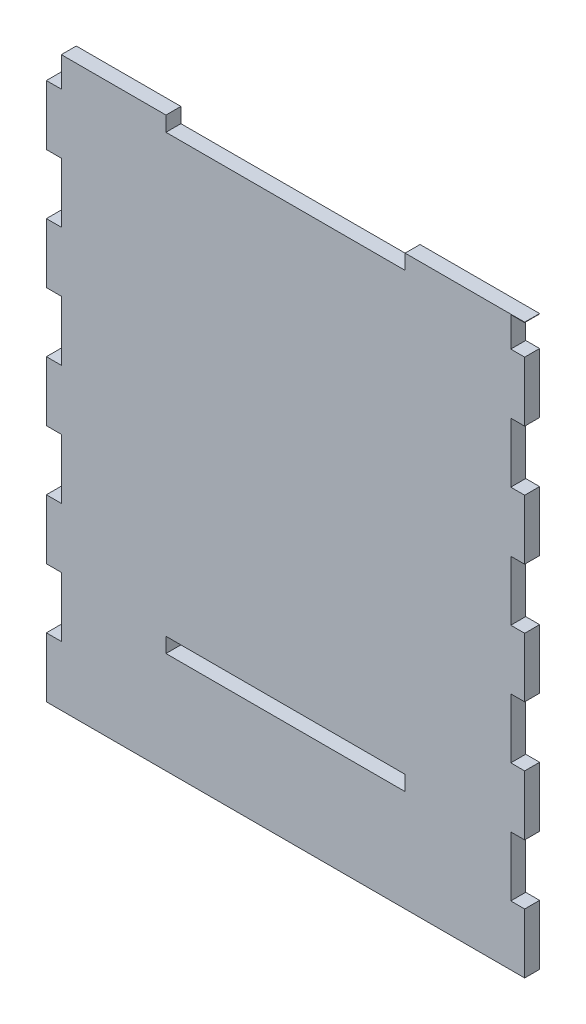
SolidWorks part; units mm, degrees
ref_plane "Front Plane" through (0, 0, 0) normal (0, 0, 1) x (1, 0, 0)
ref_plane "Top Plane" through (0, 0, 0) normal (0, 1, 0) x (1, 0, 0)
ref_plane "Right Plane" through (0, 0, 0) normal (1, 0, 0) x (0, 0, -1)
sketch "Sketch1" plane through (0, 0, 0) normal (0, 0, 1) x (1, 0, 0)
  line L1 (-202.6682, 117.9755) -> (0.5318, 117.9755)
  line L2 (-202.6682, 117.9755) -> (-202.6682, -123.3245)
  line L3 (-202.6682, -123.3245) -> (0.5318, -123.3245)
  line L4 (0.5318, 117.9755) -> (0.5318, -123.3245)
  dimension "D1" = 241.3
  dimension "D2" = 203.2
extrude "Boss-Extrude1" add sketch "Sketch1" along normal blind 6.35
sketch "Sketch2" plane through (0, 0, 6.35) normal (0, 0, 1) x (1, 0, 0)
  line L0 (-202.6682, 117.9755) -> (-202.6682, -123.3245) construction
  line L1 (-202.6682, -97.9245) -> (-196.3182, -97.9245)
  line L2 (-202.6682, -97.9245) -> (-202.6682, -72.5245)
  line L3 (-202.6682, -72.5245) -> (-196.3182, -72.5245)
  line L4 (-196.3182, -97.9245) -> (-196.3182, -72.5245)
  line L5 (-202.6682, -123.3245) -> (0.5318, -123.3245) construction
  line L6 (-202.6682, 117.9755) -> (-202.6682, -123.3245) construction
  line L7 (-202.6682, -47.1245) -> (-196.3182, -47.1245)
  line L8 (-202.6682, -47.1245) -> (-202.6682, -21.7245)
  line L9 (-202.6682, -21.7245) -> (-196.3182, -21.7245)
  line L10 (-196.3182, -47.1245) -> (-196.3182, -21.7245)
  line L11 (-202.6682, 3.6755) -> (-196.3182, 3.6755)
  line L12 (-202.6682, 3.6755) -> (-202.6682, 29.0755)
  line L13 (-202.6682, 29.0755) -> (-196.3182, 29.0755)
  line L14 (-196.3182, 3.6755) -> (-196.3182, 29.0755)
  line L15 (-202.6682, 54.4755) -> (-196.3182, 54.4755)
  line L16 (-202.6682, 54.4755) -> (-202.6682, 79.8755)
  line L17 (-202.6682, 79.8755) -> (-196.3182, 79.8755)
  line L18 (-196.3182, 54.4755) -> (-196.3182, 79.8755)
  line L19 (-202.6682, 105.2755) -> (-196.3182, 105.2755)
  line L20 (-202.6682, 105.2755) -> (-202.6682, 117.9755)
  line L21 (-202.6682, 117.9755) -> (-196.3182, 117.9755)
  line L22 (-196.3182, 105.2755) -> (-196.3182, 117.9755)
  line L23 (0.5318, 117.9755) -> (-202.6682, 117.9755) construction
  line L24 (-5.3773, -97.9245) -> (0.9727, -97.9245)
  line L25 (-5.3773, -97.9245) -> (-5.3773, -72.5245)
  line L26 (-5.3773, -72.5245) -> (0.9727, -72.5245)
  line L27 (0.9727, -97.9245) -> (0.9727, -72.5245)
  line L28 (-5.3773, -47.1245) -> (0.9727, -47.1245)
  line L29 (-5.3773, -47.1245) -> (-5.3773, -21.7245)
  line L30 (-5.3773, -21.7245) -> (0.9727, -21.7245)
  line L31 (0.9727, -47.1245) -> (0.9727, -21.7245)
  line L32 (-5.3773, 3.5082) -> (0.9727, 3.5082)
  line L33 (-5.3773, 3.5082) -> (-5.3773, 28.9082)
  line L34 (-5.3773, 28.9082) -> (0.9727, 28.9082)
  line L35 (0.9727, 3.5082) -> (0.9727, 28.9082)
  line L36 (-5.3773, 54.3082) -> (0.9727, 54.3082)
  line L37 (-5.3773, 54.3082) -> (-5.3773, 79.7082)
  line L38 (-5.3773, 79.7082) -> (0.9727, 79.7082)
  line L39 (0.9727, 54.3082) -> (0.9727, 79.7082)
  line L40 (-5.3773, 105.1082) -> (0.9727, 105.1082)
  line L41 (-5.3773, 105.1082) -> (-5.3773, 117.8082)
  line L42 (-5.3773, 117.8082) -> (0.9727, 117.8082)
  line L43 (0.9727, 105.1082) -> (0.9727, 117.8082)
  dimension "D1" = 6.35
  dimension "D2" = 25.4
  dimension "D3" = 25.4
  dimension "D4" = 25.4
  dimension "D5" = 25.4
  dimension "D6" = 6.35
  dimension "D7" = 12.7
  dimension "D8" = 25.4
  dimension "D9" = 25.4
  dimension "D10" = 25.4
  dimension "D11" = 25.4
  dimension "D12" = 25.4
  dimension "D13" = 25.4
  dimension "D14" = 25.4
  dimension "D15" = 25.4
  dimension "D16" = 6.35
  dimension "D17" = 12.7
  dimension "D18" = 25.4
  dimension "D19" = 25.4
  dimension "D20" = 25.4
  dimension "D21" = 25.4
  dimension "D22" = 25.2327
  dimension "D23" = 25.4
extrude "Cut-Extrude2" cut sketch "Sketch2" against normal blind 7.62
sketch "Sketch3" plane through (0, 117.9755, 0) normal (0, 1, 0) x (1, 0, 0)
  line L0 (0.5318, -6.35) -> (-196.3182, -6.35) construction
  line L1 (-151.8682, -6.35) -> (-50.2682, -6.35)
  line L2 (-151.8682, -6.35) -> (-151.8682, 0)
  line L3 (-151.8682, 0) -> (-50.2682, 0)
  line L4 (-50.2682, -6.35) -> (-50.2682, 0)
  line L5 (0.5318, 0) -> (-196.3182, 0) construction
  line L6 (0.5318, -6.35) -> (0.5318, 0) construction
  dimension "D1" = 101.6
  dimension "D2" = 50.8
extrude "Cut-Extrude3" cut sketch "Sketch3" against normal blind 6.35
sketch "Sketch4" plane through (0, 0, 6.35) normal (0, 0, 1) x (1, 0, 0)
  line L0 (-202.6682, -123.3245) -> (0.5318, -123.3245) construction
  line L1 (-151.8682, -73.7945) -> (-50.2682, -73.7945)
  line L2 (-151.8682, -73.7945) -> (-151.8682, -80.1445)
  line L3 (-151.8682, -80.1445) -> (-50.2682, -80.1445)
  line L4 (-50.2682, -73.7945) -> (-50.2682, -80.1445)
  line L5 (-202.6682, -47.1245) -> (-202.6682, -72.5245) construction
  point P6 (-151.8682, -76.9695)
  dimension "D1" = 43.18
  dimension "D2" = 6.35
  dimension "D3" = 101.6
  dimension "D4" = 50.8
extrude "Cut-Extrude4" cut sketch "Sketch4" against normal through all
